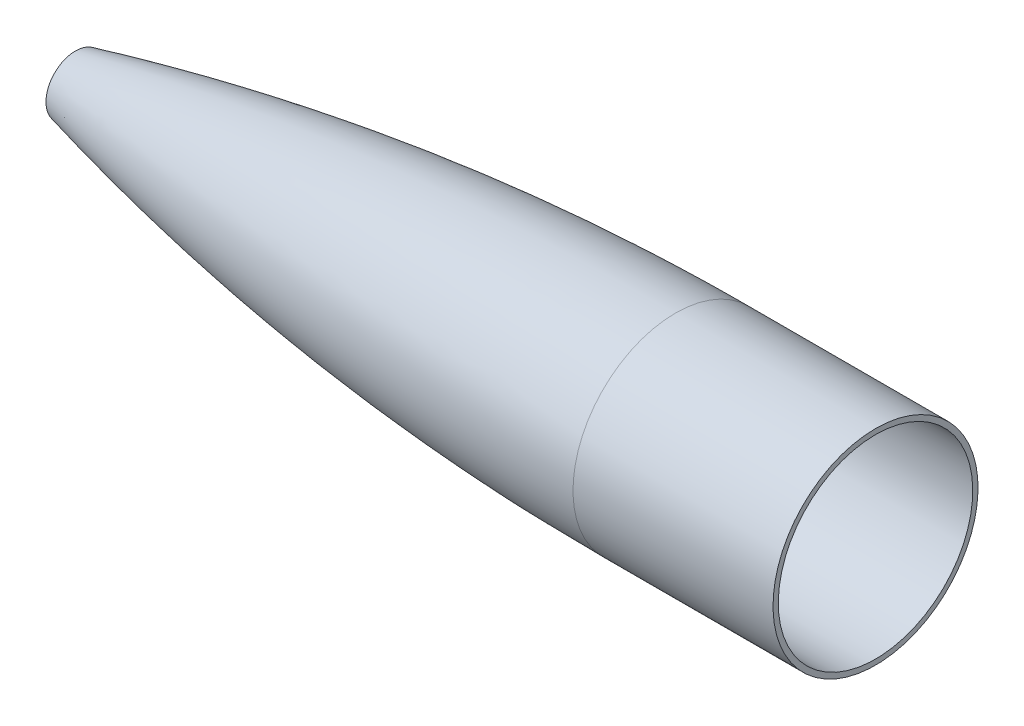
SolidWorks part; units mm, degrees
material "E-Glass Fiber"
ref_plane "Front Plane" through (0, 0, 0) normal (0, 0, 1) x (1, 0, 0)
ref_plane "Top Plane" through (0, 0, 0) normal (0, 1, 0) x (1, 0, 0)
ref_plane "Right Plane" through (0, 0, 0) normal (1, 0, 0) x (0, 0, -1)
sketch "Sketch1" plane through (0, 0, 0) normal (0, 0, 1) x (1, 0, 0)
  line L0 (304.8, 37.1184) -> (304.8, -14.9516)
  line L1 (304.8, -14.9516) -> (0, -14.9516)
  line L2 (0, 0) -> (0, -14.9516)
  spline S0 degree 4 poles (-29.5659, -7.6879) (-28.944, -7.5182) (-27.7002, -7.1797) (-25.2157, -6.507) (-22.11, -5.6753) (-19.0276, -4.8585) (-15.9328, -4.0476) (-13.5077, -3.4169) (-11.0085, -2.7731) (-8.655, -2.1705) (-6.0075, -1.5004) (-3.9434, -0.9797) (-0.8619, -0.2129) (0.5469, 0.1357) (3.1013, 0.7635) (5.1043, 1.2515) (7.1182, 1.7387) (9.1692, 2.2315) (11.2056, 2.7171) (13.2459, 3.2001) (15.8196, 3.805) (18.9274, 4.528) (22.5707, 5.3649) (26.7504, 6.3101) (31.9791, 7.4741) (46.634, 10.6673) (68.6856, 15.1354) (117.2008, 23.8345) (168.235, 30.3998) (212.0224, 34.1387) (248.4065, 35.8891) (258.0412, 36.2658) (264.4656, 36.4808) (268.749, 36.6097) (273.0328, 36.7241) (277.317, 36.824) (281.6014, 36.9095) (285.3391, 36.9715) (288.5296, 37.0155) (291.1732, 37.046) (293.2698, 37.0668) (295.3633, 37.0841) (297.4725, 37.098) (299.5447, 37.1083) (301.6057, 37.1153) (304.2352, 37.1189) (305.6848, 37.1186) (308.8537, 37.1138) (310.9791, 37.1038) (313.7032, 37.0887) (316.1275, 37.0687) (318.703, 37.0436) (321.2018, 37.0134) (323.7511, 36.9782) (326.2919, 36.9376) (328.8547, 36.8917) (331.4234, 36.8404) (333.3523, 36.798) (334.6374, 36.768) (335.2799, 36.7526) knots 0 0 0 0 0 0.006986 0.013973 0.027946 0.034806 0.041666 0.048526 0.055386 0.062246 0.069106 0.075966 0.082827 0.088511 0.094195 0.099879 0.105563 0.111247 0.116931 0.122615 0.128299 0.139917 0.151536 0.163154 0.174773 0.19801 0.314194 0.407142 0.709223 0.755697 0.790552 0.802171 0.813789 0.825408 0.837026 0.848645 0.860263 0.871882 0.877566 0.88325 0.888934 0.894618 0.900302 0.905986 0.91167 0.917354 0.924199 0.931044 0.937889 0.944735 0.95158 0.958425 0.96527 0.972115 0.979087 0.986058 0.993029 1 1 1 1 1 construction
  spline S1 degree 4 poles (0, 0) (0.4246, 0.105) (1.2797, 0.3158) (3.1013, 0.7635) (5.1043, 1.2515) (7.1182, 1.7387) (9.1692, 2.2315) (11.2056, 2.7171) (13.2459, 3.2001) (15.8196, 3.805) (18.9274, 4.528) (22.5707, 5.3649) (26.7504, 6.3101) (31.9791, 7.4741) (46.634, 10.6673) (68.6856, 15.1354) (117.2008, 23.8345) (168.235, 30.3998) (212.0224, 34.1387) (248.4065, 35.8891) (258.0412, 36.2658) (264.4656, 36.4808) (268.749, 36.6097) (273.0328, 36.7241) (277.317, 36.824) (281.6014, 36.9095) (285.3391, 36.9715) (288.5296, 37.0155) (291.1732, 37.046) (293.2698, 37.0668) (295.3633, 37.0841) (297.4725, 37.098) (299.5447, 37.1083) (301.6057, 37.1153) (303.482, 37.1179) (304.3626, 37.1184) (304.8, 37.1184) knots 0.082827 0.082827 0.082827 0.082827 0.082827 0.088511 0.094195 0.099879 0.105563 0.111247 0.116931 0.122615 0.128299 0.139917 0.151536 0.163154 0.174773 0.19801 0.314194 0.407142 0.709223 0.755697 0.790552 0.802171 0.813789 0.825408 0.837026 0.848645 0.860263 0.871882 0.877566 0.88325 0.888934 0.894618 0.900302 0.905986 0.91167 0.917354 0.917354 0.917354 0.917354 0.917354
  dimension "D1" = 52.07
  dimension "D2" = 304.8
revolve "Revolve1" add sketch "Sketch1" angle 360 about L1
shell "Shell1" thickness 2.286 removed face at (304.8, 37.1184, 0) removed face at (0, 0, 0)
ref_plane "Plane1" through (304.8, 0, 0) normal (1, 0, 0) x (0, 0, -1)
sketch "Sketch4" plane through (304.8, 0, 0) normal (1, 0, 0) x (0, 0, -1)
  circle A0 centre (0, -14.9516) radius 49.3903
  circle A1 centre (0, -14.9516) radius 52.07
  circle A2 centre (0, -14.9516) radius 52.07 construction
  dimension "D1" = 104.14
  dimension "D2" = 98.7806
extrude "Boss-Extrude2" add sketch "Sketch4" along normal blind 101.6
